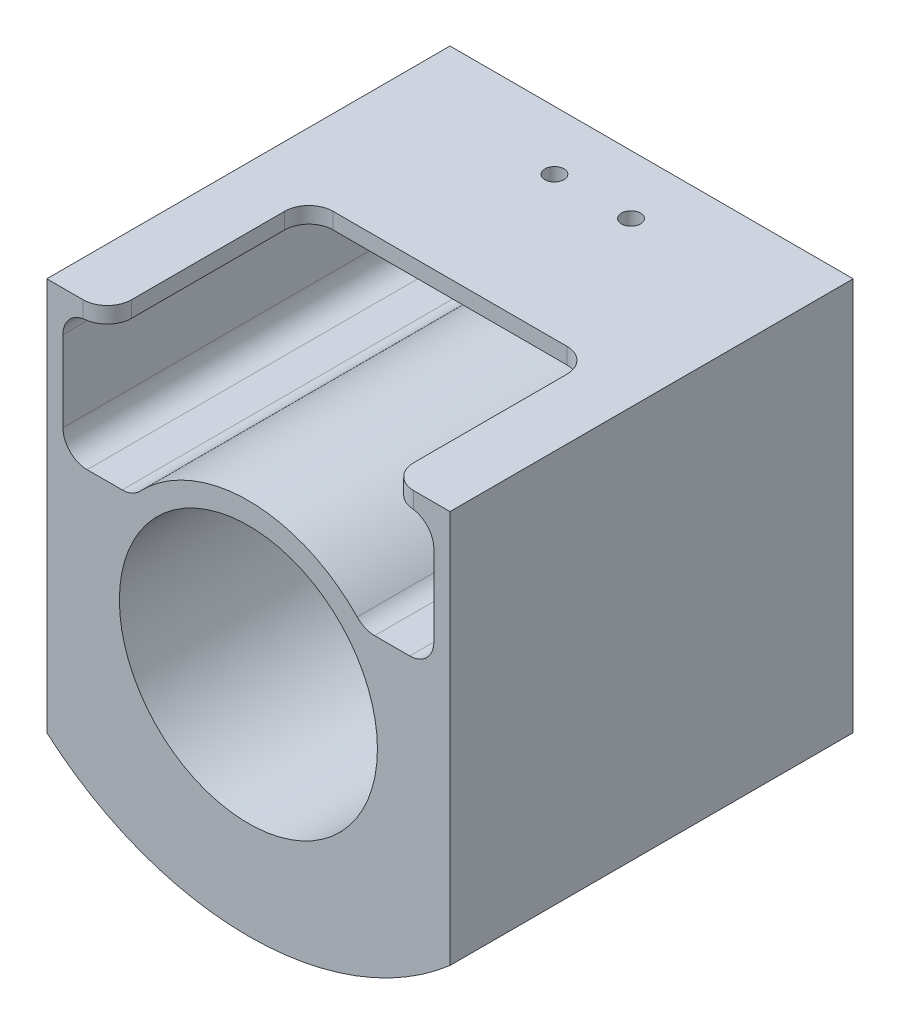
SolidWorks part; units mm, degrees
ref_plane "Front Plane" through (0, 0, 0) normal (0, 0, 1) x (1, 0, 0)
ref_plane "Top Plane" through (0, 0, 0) normal (0, 1, 0) x (1, 0, 0)
ref_plane "Right Plane" through (0, 0, 0) normal (1, 0, 0) x (0, 0, -1)
sketch "Sketch1" plane through (0, 0, 0) normal (0, 0, 1) x (1, 0, 0)
  line L1 (0, 0) -> (0, -38.1) construction
  line L2 (-25, 0) -> (-25, -28.7508)
  line L3 (25, 0) -> (25, -28.7508)
  line L4 (-25, 0) -> (-25, 20)
  line L5 (-25, 20) -> (25, 20)
  line L6 (25, 20) -> (25, 0)
  arc A0 (-25, -28.7508) -> (25, -28.7508) centre (0, 0) ccw
  dimension "D1" = 76.2
  dimension "D2" = 50
  dimension "D3" = 20
extrude "Boss-Extrude2" add sketch "Sketch1" along normal blind 50
sketch "Sketch2" plane through (0, 0, 50) normal (0, 0, 1) x (1, 0, 0)
  line L6 (0, 6) -> (0, -26) construction
  circle A0 centre (0, -10) radius 16
  dimension "D2" = 32
  dimension "D1" = 10
extrude "Cut-Extrude1" cut sketch "Sketch2" against normal through all both
sketch "Sketch4" plane through (0, 0, 50) normal (0, 0, 1) x (1, 0, 0)
  line L0 (-23, 18) -> (23, 18)
  line L3 (0, 20) -> (0, 6) construction
  line L4 (25, 20) -> (-25, 20) construction
  line L5 (23, 2) -> (14.3178, 2)
  line L6 (-23, 18) -> (-23, 2)
  line L7 (-23, 2) -> (-14.3178, 2)
  line L8 (-25, 20) -> (-25, -28.7508) construction
  line L9 (23, 18) -> (23, 2)
  circle A2 centre (0, -10) radius 16 construction
  arc A3 (14.3178, 2) -> (-14.3178, 2) centre (0, -10) ccw
  point P2 (0, 13)
  point P14 (0, 18)
  dimension "D1" = 37.3631
  dimension "D2" = 2
  dimension "D3" = 2
  dimension "D4" = 16
extrude "Cut-Extrude3" cut sketch "Sketch4" against normal through all
fillet "Fillet1" radius 3 6 edges at (23, 18, 25) (23, 2, 25) (14.3178, 2, 25) (-14.3178, 2, 25) (-23, 2, 25) (-23, 18, 25)
sketch "Sketch5" plane through (0, 20, 0) normal (0, 1, 0) x (1, 0, 0)
  line L0 (25, -50) -> (-25, -50) construction
  line L1 (-17.5, -50) -> (17.5, -50)
  line L2 (-17.5, -50) -> (-17.5, -25)
  line L3 (-17.5, -25) -> (17.5, -25)
  line L4 (17.5, -50) -> (17.5, -25)
  line L5 (0, 0) -> (0, -50) construction
  dimension "D1" = 35
  dimension "D2" = 25
extrude "Cut-Extrude4" cut sketch "Sketch5" against normal blind 10
fillet "Fillet2" radius 3 4 edges at (17.5, 19, 50) (17.5, 19, 25) (-17.5, 19, 25) (-17.5, 19, 50)
ref_plane "Plane1" through (0, 0, 14) normal (0, 0, 1) x (1, 0, 0)
sketch "Sketch6" plane through (0, 0, 14) normal (0, 0, 1) x (1, 0, 0)
  arc A0 (16, -10) -> (-16, -10) centre (0, -10) ccw
  circle A1 centre (0, -10) radius 16 construction
  arc A2 (16, -10) -> (-16, -10) centre (0, -10) cw
  circle A3 centre (0, -10) radius 9.5
  circle A4 centre (0, 3) radius 1.25
  circle A5 centre (13, -10) radius 1.25
  circle A6 centre (-13, -10) radius 1.25
  circle A7 centre (0, -23) radius 1.25
  dimension "D1" = 19
  dimension "D6" = 2.5
  dimension "D2" = 13
  dimension "D3" = 13
  dimension "D4" = 13
  dimension "D5" = 13
extrude "Boss-Extrude3" add sketch "Sketch6" against normal blind 5
sketch "Sketch7" plane through (0, 0, 0) normal (1, 0, 0) x (0, 0, -1)
  circle A0 centre (-40, -32) radius 2.5
  circle A1 centre (-10, -32) radius 2.5
  dimension "D3" = 5
  dimension "D1" = 32
  dimension "D2" = 10
  dimension "D4" = 30
extrude "Cut-Extrude5" cut sketch "Sketch7" against normal through all both and the other way through all
sketch "Sketch8" plane through (0, 20, 0) normal (0, 1, 0) x (1, 0, 0)
  line L0 (0, 0) -> (0, -25) construction
  line L1 (25, 0) -> (-25, 0) construction
  line L2 (14.5, -25) -> (-14.5, -25) construction
  circle A0 centre (-4.75, -7.3) radius 1.175
  circle A1 centre (4.75, -7.3) radius 1.175
  dimension "D1" = 2.35
  dimension "D2" = 9.5
  dimension "D3" = 7.3
extrude "Cut-Extrude6" cut sketch "Sketch8" against normal up to next contours A0 | A1
